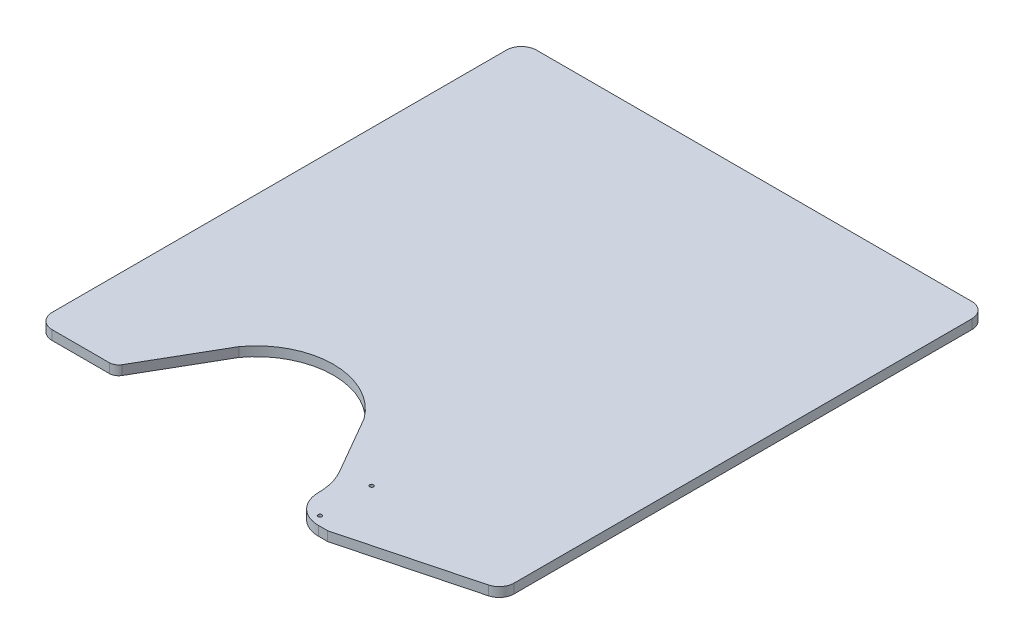
SolidWorks part; units mm, degrees
material "ABS PC"
ref_plane "Plan de face" through (0, 0, 0) normal (0, 0, 1) x (1, 0, 0)
ref_plane "Plan de dessus" through (0, 0, 0) normal (0, 1, 0) x (1, 0, 0)
ref_plane "Plan de droite" through (0, 0, 0) normal (1, 0, 0) x (0, 0, -1)
sketch "Esquisse1" plane through (0, 0, 0) normal (0, 1, 0) x (1, 0, 0)
  line L0 (-60.6815, -188.3301) -> (-75.8539, -214.6094) construction
  line L1 (-115.5, 31.2) -> (115.5, 31.2)
  line L2 (-123.5, 23.2) -> (-123.5, -217.8)
  line L3 (-60.6815, -188.3301) -> (-75.8539, -214.6094)
  line L4 (123.5, 23.2) -> (123.5, -219.6281)
  line L5 (25.8539, -214.6094) -> (10.6815, -188.3301) construction
  line L6 (25.8539, -214.6094) -> (10.6815, -188.3301)
  line L7 (8.1815, -184) -> (10.6815, -188.3301)
  line L8 (-58.1815, -184) -> (-60.6815, -188.3301)
  line L9 (-115.5, -225.8) -> (-85.2015, -225.8)
  line L10 (117.5301, -227.3662) -> (50, -245.0829)
  line L11 (45, -245.0829) -> (50, -245.0829) construction
  line L12 (45, -245.0829) -> (50, -245.0829)
  line L13 (-80.8714, -223.3) -> (-75.8539, -214.6094)
  line L14 (-118.5, -220.8) -> (-108.5, -220.8) construction
  line L15 (-118.5, -220.8) -> (-118.5, 31.2) construction
  line L16 (118.5, -220.8) -> (118.5, 31.2) construction
  line L18 (108.5, 31.2) -> (-108.5, 31.2) construction
  arc A0 (8.1815, -184) -> (-58.1815, -184) centre (-25, -208.0829) ccw construction
  arc A1 (8.1815, -184) -> (-58.1815, -184) centre (-25, -208.0829) ccw
  arc A3 (36.2863, -217.8734) -> (45, -245.0829) centre (45, -230.0829) ccw construction
  arc A4 (30, -230.0829) -> (45, -245.0829) centre (45, -230.0829) ccw
  arc A5 (30, -230.0829) -> (25.8539, -214.6094) centre (-0.9469, -230.0829) ccw construction
  arc A6 (30, -230.0829) -> (25.8539, -214.6094) centre (-0.9469, -230.0829) ccw
  arc A7 (-85.2015, -225.8) -> (-80.8714, -223.3) centre (-85.2015, -220.8) ccw
  circle A8 centre (41, -212.75) radius 1
  circle A9 centre (41, -240.25) radius 1
  arc A10 (-115.5, 31.2) -> (-123.5, 23.2) centre (-115.5, 23.2) ccw
  arc A11 (115.5, 31.2) -> (123.5, 23.2) centre (115.5, 23.2) cw
  arc A12 (117.5301, -227.3662) -> (123.5, -219.6281) centre (115.5, -219.6281) ccw
  arc A13 (-123.5, -217.8) -> (-115.5, -225.8) centre (-115.5, -217.8) ccw
  point P44 (123.5, -225.8)
  dimension "D1" = 5
  dimension "D2" = 2
  dimension "D6" = 8
  dimension "D3" = 5
  dimension "D4" = 5
  dimension "D5" = 5
extrude "Boss.-Extru.1" add sketch "Esquisse1" against normal blind 5
